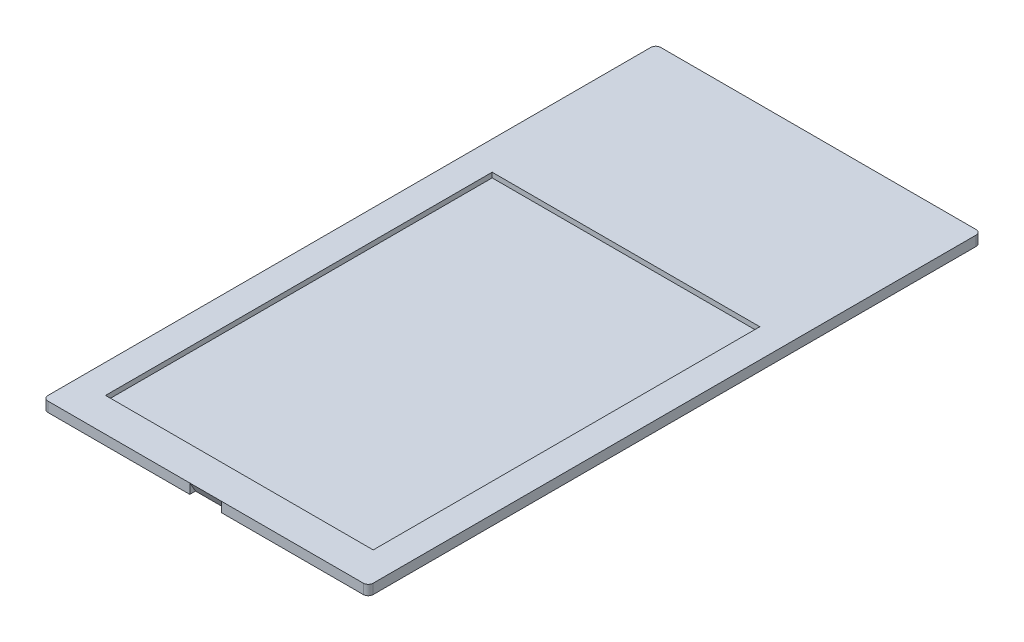
SolidWorks part; units mm, degrees
ref_plane "前视基准面" through (0, 0, 0) normal (0, 0, 1) x (1, 0, 0)
ref_plane "上视基准面" through (0, 0, 0) normal (0, 1, 0) x (1, 0, 0)
ref_plane "右视基准面" through (0, 0, 0) normal (1, 0, 0) x (0, 0, -1)
other "Configuration Table"
ref_axis "基准轴1" through (-62.5864, 0, 0) along (1, 0, 0)
sketch "草图1" plane through (0, 0, 0) normal (0, 1, 0) x (1, 0, 0)
  line L1 (-32.8, -2.2) -> (32.8, -2.2)
  line L2 (-32.8, -2.2) -> (-32.8, -125.8)
  line L3 (-32.8, -125.8) -> (32.8, -125.8)
  line L4 (32.8, -2.2) -> (32.8, -125.8)
  line L8 (34, 0) -> (-34, 0) construction
  line L9 (-34, -128) -> (34, -128) construction
  line L10 (35, -127) -> (35, -1) construction
  line L11 (-35, -1) -> (-35, -127) construction
  point P4 (35, -2.5605)
  point P5 (33.5209, -126.5608)
  point P6 (-32.9506, -126.0629)
  dimension "D1" = 2.2
  dimension "D2" = 2.2
  dimension "D3" = 2.2
  dimension "D4" = 2.2
extrude "凸台-拉伸1" add sketch "草图1" against normal up to surface (2 mm away)
sketch "草图4" plane through (0, 0, 0) normal (1, 0, 0) x (0, 0, -1)
  line L4 (-125.8, 0) -> (-124.6453, -2)
  line L5 (-125.8, -2) -> (-2.2, -2) construction
  line L6 (-124.6453, -2) -> (-125.8, -2)
  line L7 (-125.8, -2) -> (-125.8, 0)
  line L8 (-2.2, 0) -> (-2.2, -2)
  line L9 (-2.2, -2) -> (-3.3547, -2)
  line L10 (-3.3547, -2) -> (-2.2, 0)
  dimension "D1" = 30
extrude "切除-拉伸3" cut sketch "草图4" against normal mid plane 6.4
sketch "草图3" plane through (0, 0, 0) normal (0, 1, 0) x (1, 0, 0)
  line L0 (0, -41) -> (0, 0) construction
  line L1 (-27, -41) -> (27, -41)
  line L2 (-27, -41) -> (-27, -119)
  line L3 (-27, -119) -> (27, -119)
  line L4 (27, -41) -> (27, -119)
  line L5 (24, -43) -> (-24, -43) construction
  line L6 (-24, -117) -> (24, -117) construction
  line L8 (25, -116) -> (25, -44) construction
  dimension "D1" = 2
  dimension "D2" = 2
  dimension "D3" = 54
  dimension "D4" = 78
  dimension "D5" = 2
extrude "切除-拉伸2" cut sketch "草图3" against normal blind 1
fillet "圆角1" radius 1 4 edges at (-32.8, -1, 2.2) (-32.8, -1, 125.8) (32.8, -1, 125.8) (32.8, -1, 2.2)
